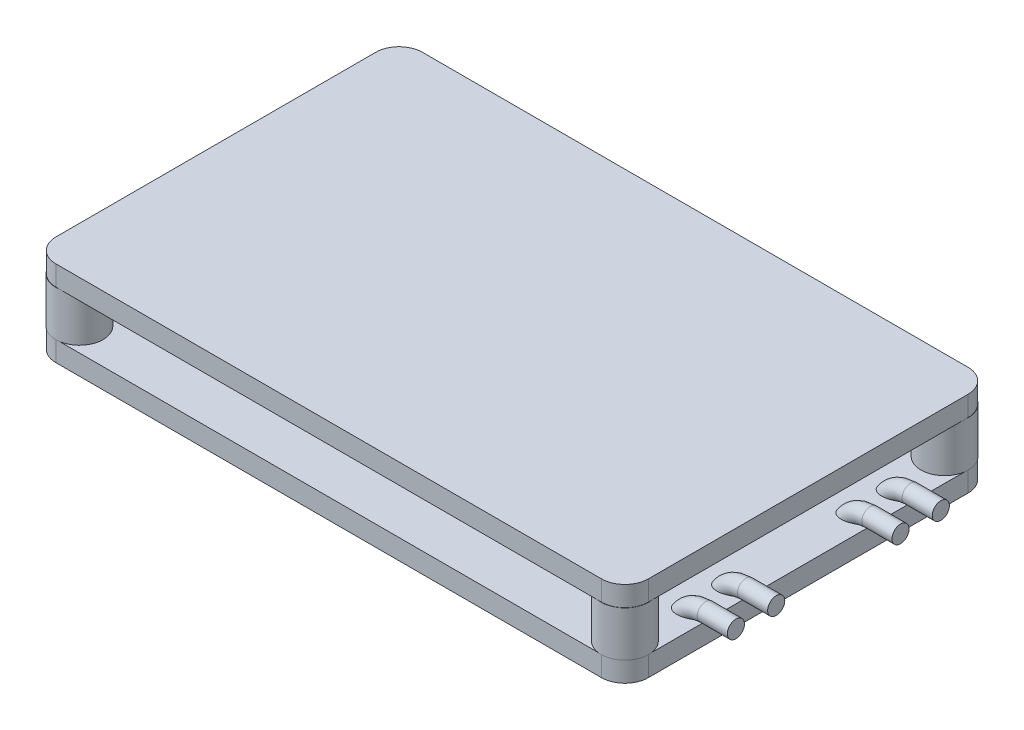
SolidWorks part; units mm, degrees
ref_plane "Front" through (0, 0, 0) normal (0, 0, 1) x (1, 0, 0)
ref_plane "Top" through (0, 0, 0) normal (0, 1, 0) x (1, 0, 0)
ref_plane "Right" through (0, 0, 0) normal (1, 0, 0) x (0, 0, -1)
sketch "Sketch1" plane through (0, 0, 0) normal (0, 1, 0) x (1, 0, 0)
  line L1 (-29.415, -18.2) -> (29.415, -18.2)
  line L2 (-29.415, -18.2) -> (-29.415, 18.2)
  line L3 (-29.415, 18.2) -> (29.415, 18.2)
  line L4 (29.415, -18.2) -> (29.415, 18.2)
  line L5 (-29.415, -18.2) -> (29.415, 18.2) construction
  line L6 (-29.415, 18.2) -> (29.415, -18.2) construction
  arc A0 (29.415, 15.875) -> (27.09, 18.2) centre (27.09, 15.875) ccw
  arc A1 (-27.09, 18.2) -> (-29.415, 15.875) centre (-27.09, 15.875) ccw
  arc A2 (-29.415, -15.875) -> (-27.09, -18.2) centre (-27.09, -15.875) ccw
  arc A3 (27.09, -18.2) -> (29.415, -15.875) centre (27.09, -15.875) ccw
  point P0 (0, 0)
  point P14 (27.09, 18.2)
  point P15 (-27.09, 18.2)
  point P16 (29.415, 15.875)
  point P17 (-29.415, 15.875)
  point P18 (-29.415, -15.875)
  point P19 (27.09, -18.2)
  point P20 (-27.09, -18.2)
  point P21 (29.415, -15.875)
  dimension "D1" = 58.83
  dimension "D2" = 36.4
  dimension "D3" = 31.75
extrude "Boss-Extrude1" add sketch "Sketch1" along normal blind 2 contours L1 A3 L4 A0 L3 A1 L2 A2 region at (0, 0, 0)
sketch "Sketch2" plane through (0, 2, 0) normal (0, 1, 0) x (1, 0, 0)
  line L1 (-27.09, 15.875) -> (27.09, 15.875) construction
  line L2 (-27.09, 15.875) -> (-27.09, -15.875) construction
  line L3 (-27.09, -15.875) -> (27.09, -15.875) construction
  line L4 (27.09, 15.875) -> (27.09, -15.875) construction
  circle A0 centre (-27.09, -15.875) radius 2.35
  circle A2 centre (-27.09, 15.875) radius 2.35
  circle A3 centre (27.09, 15.875) radius 2.35
  circle A4 centre (27.09, -15.875) radius 2.35
  arc A6 (-29.415, -15.875) -> (-27.09, -18.2) centre (-27.09, -15.875) ccw construction
  arc A7 (27.09, -18.2) -> (29.415, -15.875) centre (27.09, -15.875) ccw construction
  arc A8 (-27.09, 18.2) -> (-29.415, 15.875) centre (-27.09, 15.875) ccw construction
  dimension "D1" = 4.7
extrude "Boss-Extrude2" add sketch "Sketch2" along normal blind 4.5
extrude "Boss-Extrude3" add sketch "Sketch1<3>" along normal blind 2 from surface contours L1 A3 L4 A0 L3 A1 L2 A2 region at (0, 0, 0) starting at face at (-27.09, 6.5, -13.525)
sketch "Sketch1<3>" plane through (0, 0, 0) normal (0, 1, 0) x (1, 0, 0) same geometry as "Sketch1"
sketch "Sketch4" plane through (0, 0, 0) normal (1, 0, 0) x (0, 0, -1)
  line L0 (6.175, 2.85) -> (10.175, 2.85) construction
  line L1 (11.025, 2.85) -> (13.525, 2.85) construction
  line L2 (-10.175, 2.85) -> (-6.175, 2.85) construction
  line L3 (13.525, 6.5) -> (13.525, 2) construction
  line L4 (-6.175, 2.85) -> (6.175, 2.85) construction
  line L5 (-13.525, 2) -> (-18.2, 2) construction
  circle A0 centre (10.175, 2.85) radius 0.85
  circle A1 centre (6.175, 2.85) radius 0.85
  circle A2 centre (-6.175, 2.85) radius 0.85
  circle A3 centre (-10.175, 2.85) radius 0.85
  point P8 (11.025, 2.85)
  point P13 (0, 2.85)
  point P17 (-8.175, 2.85)
  point P18 (8.175, 2.85)
  dimension "D1" = 1.7
  dimension "D2" = 4
  dimension "D3" = 2.5
extrude "Boss-Extrude4" add sketch "Sketch4" along normal blind 3 from surface separate body starting at face at (29.415, 7.1667, 0)
sketch "Sketch5" plane through (29.415, 0, 0) normal (-1, 0, 0) x (0, 0, 1)
  circle A0 centre (10.175, 2.85) radius 0.85 construction
  circle A1 centre (6.175, 2.85) radius 0.85 construction
  circle A2 centre (-6.175, 2.85) radius 0.85 construction
  circle A3 centre (-10.175, 2.85) radius 0.85 construction
  circle A4 centre (10.175, 2.85) radius 0.85
  circle A5 centre (6.175, 2.85) radius 0.85
  circle A6 centre (-6.175, 2.85) radius 0.85
  circle A7 centre (-10.175, 2.85) radius 0.85
revolve "Revolve2" add sketch "Sketch5" angle 90 about axis through (29.415, 0, 0) along (0, 0, -1) reverse direction yes
extrude "Boss-Extrude5" add sketch "Sketch4<2>" against normal blind 3 from surface separate body contours A1 | A0 region at (0, 2.85, -10.175) region at (0, 2.85, -6.175) starting at face at (-29.415, 7.1667, 0)
sketch "Sketch4<2>" plane through (0, 0, 0) normal (1, 0, 0) x (0, 0, -1) same geometry as "Sketch4"
sketch "Sketch6" plane through (-29.415, 0, 0) normal (1, 0, 0) x (0, 0, -1)
  circle A0 centre (10.175, 2.85) radius 0.85 construction
  circle A1 centre (6.175, 2.85) radius 0.85 construction
  circle A2 centre (10.175, 2.85) radius 0.85
  circle A3 centre (6.175, 2.85) radius 0.85
revolve "Revolve3" add sketch "Sketch6" angle 90 about axis through (-29.415, 0, 0) along (0, 0, -1)
